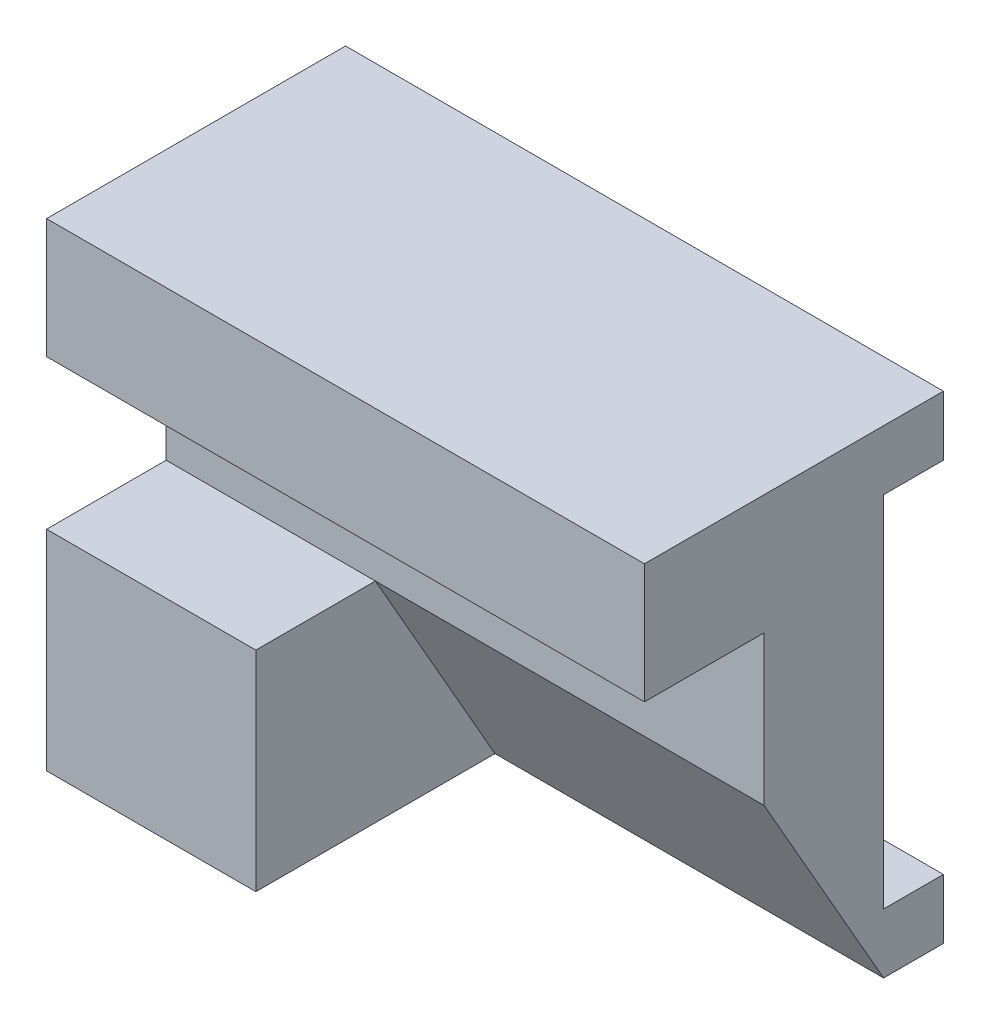
SolidWorks part; units mm, degrees
ref_plane "Front Plane" through (0, 0, 0) normal (0, 0, 1) x (1, 0, 0)
ref_plane "Top Plane" through (0, 0, 0) normal (0, 1, 0) x (1, 0, 0)
ref_plane "Right Plane" through (0, 0, 0) normal (1, 0, 0) x (0, 0, -1)
sketch "Sketch1" plane through (0, 0, 0) normal (0, 0, 1) x (1, 0, 0)
  line L0 (0, -20) -> (100, -20)
  line L1 (0, 0) -> (100, 0)
  line L2 (0, 0) -> (0, -80)
  line L3 (0, -80) -> (100, -80)
  line L4 (100, 0) -> (100, -80)
  line L5 (0, -45) -> (100, -45)
  line L6 (35, -45) -> (35, -80)
  circle A0 centre (15, -32.5) radius 6
  circle A1 centre (75, -32.5) radius 6
  dimension "D5" = 12
  dimension "D6" = 12
  dimension "D1" = 80
  dimension "D2" = 100
  dimension "D3" = 20
  dimension "D4" = 35
  dimension "D7" = 15
  dimension "D8" = 60
  dimension "D9" = 47.5
  dimension "D10" = 35
extrude "Boss-Extrude1" add sketch "Sketch1" along normal blind 20 contours L2 L5 L4 L0 A1 A0 | L5 L6 L3 L4 region at (50.4974, -32.5, 0) region at (67.5, -62.5, 0)
extrude "Boss-Extrude2" add sketch "Sketch1<3>" along normal blind 40 contours L6 L5 L2 L3 | L4 L1 L2 L0 region at (50, -10, 0) region at (17.5, -62.5, 0)
sketch "Sketch1<3>" plane through (0, 0, 0) normal (0, 0, 1) x (1, 0, 0) same geometry as "Sketch1"
sketch "Sketch3" plane through (0, 0, 0) normal (1, 0, 0) x (0, 0, -1)
  line L1 (0, -80) -> (10, -80)
  line L2 (0, -80) -> (0, -70)
  line L3 (0, -70) -> (10, -70)
  line L4 (10, -80) -> (10, -70)
  line L5 (0, 0) -> (10, 0)
  line L6 (0, 0) -> (0, -10)
  line L7 (0, -10) -> (10, -10)
  line L8 (10, 0) -> (10, -10)
  dimension "D1" = 10
  dimension "D2" = 10
extrude "Boss-Extrude4" add sketch "Sketch3" along normal up to surface (100 mm away) up to face at (100, -33.3333, 20)
sketch "Sketch4" plane through (100, 0, 0) normal (1, 0, 0) x (0, 0, -1)
  line L0 (-20, -45) -> (0, -80)
  line L1 (-20, -80) -> (10, -80) construction
  line L2 (0, -80) -> (-20, -80)
  line L3 (-20, -80) -> (-20, -45)
  point P5 (0, 0)
extrude "Cut-Extrude1" cut sketch "Sketch4" against normal up to surface (65 mm away) up to face at (35, -62.5, 30)
